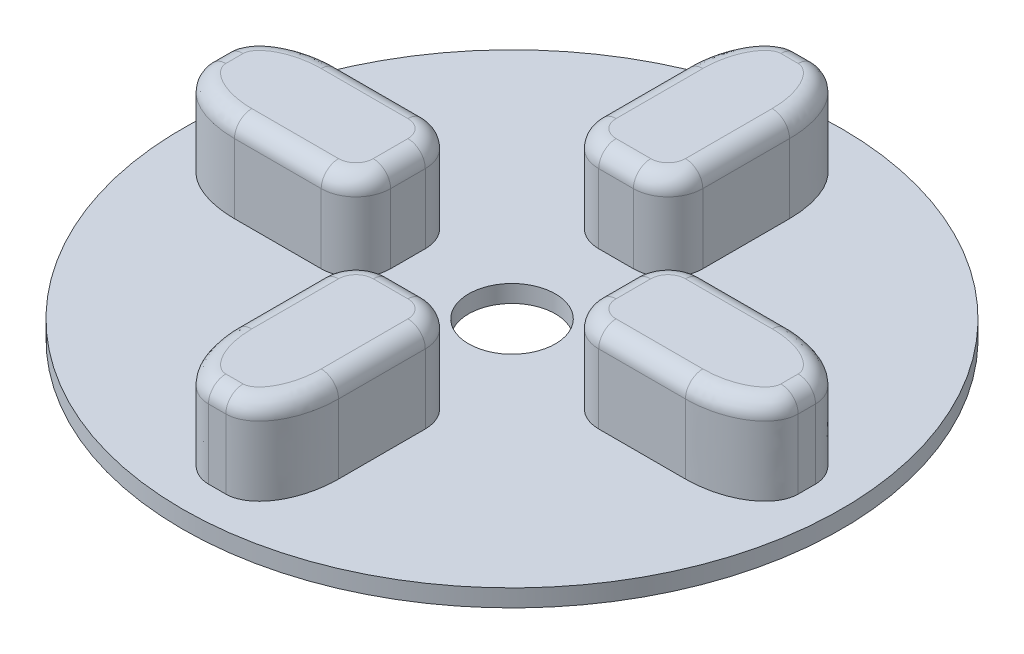
SolidWorks part; units mm, degrees
ref_plane "Front Plane" through (0, 0, 0) normal (0, 0, 1) x (1, 0, 0)
ref_plane "Top Plane" through (0, 0, 0) normal (0, 1, 0) x (1, 0, 0)
ref_plane "Right Plane" through (0, 0, 0) normal (1, 0, 0) x (0, 0, -1)
sketch "Sketch1" plane through (0, 0, 0) normal (0, 1, 0) x (1, 0, 0)
  circle A0 centre (0, 0) radius 19
  dimension "D1" = 38
extrude "Base" add sketch "Sketch1" along normal blind 1
sketch "Sketch2" plane through (0, 1, 0) normal (0, 1, 0) x (1, 0, 0)
  circle A0 centre (0, 0) radius 13 construction
  circle A1 centre (0, 13) radius 4.5
  circle A2 centre (13, 0) radius 4.5
  circle A3 centre (0, -13) radius 4.5
  circle A4 centre (-13, 0) radius 4.5
  point P14 (0, 0)
  dimension "D1" = 26
  dimension "D2" = 9
  dimension "D3" = 4
extrude "Buttons" [suppressed] add sketch "Sketch2" along normal blind 6
fillet "Fillet1" [suppressed] radius 1
hole_wizard "Ø5.0mm Dowel Hole1" positions "Sketch3" profile "Sketch4" hole size "Ø5.0" standard "ANSI Metric" end condition through all
sketch "Sketch3" plane through (0, 1, 0) normal (0, 1, 0) x (1, 0, 0)
  point P0 (0, 0)
sketch "Sketch4" plane through (0, 1, 0) normal (1, 0, 0) x (0, 0, 1)
  line L0 (0, 0) -> (0, 1)
  line L1 (0, 1) -> (2.5, 1)
  line L2 (2.5, 1) -> (2.5, 0)
  line L5 (2.5, 0) -> (0, 0)
  line L11 (0, -6.35) -> (0, 107.95) construction
  dimension "Thru Hole Dia." = 5
  dimension "Thru Hole Depth" = 1
sketch "Sketch5" plane through (0, 1, 0) normal (0, 1, 0) x (1, 0, 0)
  line L0 (6, 3) -> (6, -3)
  line L1 (-3, 6) -> (3, 6)
  line L2 (-3, 6) -> (-3, 17)
  line L3 (-3, 17) -> (3, 17)
  line L4 (3, 6) -> (3, 17)
  line L5 (-3, 6) -> (3, 17) construction
  line L6 (-3, 17) -> (3, 6) construction
  line L7 (6, 3) -> (17, 3)
  line L8 (17, 3) -> (17, -3)
  line L9 (6, -3) -> (17, -3)
  line L10 (6, 3) -> (17, -3) construction
  line L11 (17, 3) -> (6, -3) construction
  line L12 (3, -6) -> (-3, -6)
  line L13 (3, -6) -> (3, -17)
  line L14 (3, -17) -> (-3, -17)
  line L15 (-3, -6) -> (-3, -17)
  line L16 (3, -6) -> (-3, -17) construction
  line L17 (3, -17) -> (-3, -6) construction
  line L18 (-6, -3) -> (-6, 3)
  line L19 (-6, -3) -> (-17, -3)
  line L20 (-17, -3) -> (-17, 3)
  line L21 (-6, 3) -> (-17, 3)
  line L22 (-6, -3) -> (-17, 3) construction
  line L23 (-17, -3) -> (-6, 3) construction
  circle A0 centre (0, 0) radius 11.5 construction
  point P3 (0, 11.5)
  point P8 (7.6768, -3.3592)
  point P9 (0, 0)
  point P11 (11.5, 0)
  point P16 (0, -11.5)
  point P21 (-11.5, 0)
  point P26 (0, 0)
  dimension "D1" = 23
  dimension "D2" = 6
  dimension "D3" = 11
  dimension "D4" = 4
extrude "D-Pad" add sketch "Sketch5" along normal blind 5
fillet "Fillet2" radius 2 8 edges at (3, 3.5, 6) (-3, 3.5, 6) (6, 3.5, -3) (6, 3.5, 3) (-6, 3.5, 3) (-6, 3.5, -3) (-3, 3.5, -6) (3, 3.5, -6)
fillet "Fillet3" radius 2.5 8 edges at (-17, 3.5, -3) (-17, 3.5, 3) (-3, 3.5, 17) (3, 3.5, 17) (17, 3.5, 3) (17, 3.5, -3) (-3, 3.5, -17) (3, 3.5, -17)
fillet "Fillet4" radius 1 32 edges at (-6.5858, 6, -2.4142) (-6, 6, 0) (-6.5858, 6, 2.4142) (-2.4142, 6, 6.5858) (0, 6, 6) (2.4142, 6, 6.5858) (6.5858, 6, 2.4142) (6, 6, 0) (6.5858, 6, -2.4142) (2.4142, 6, -6.5858) (0, 6, -6) (-2.4142, 6, -6.5858)
